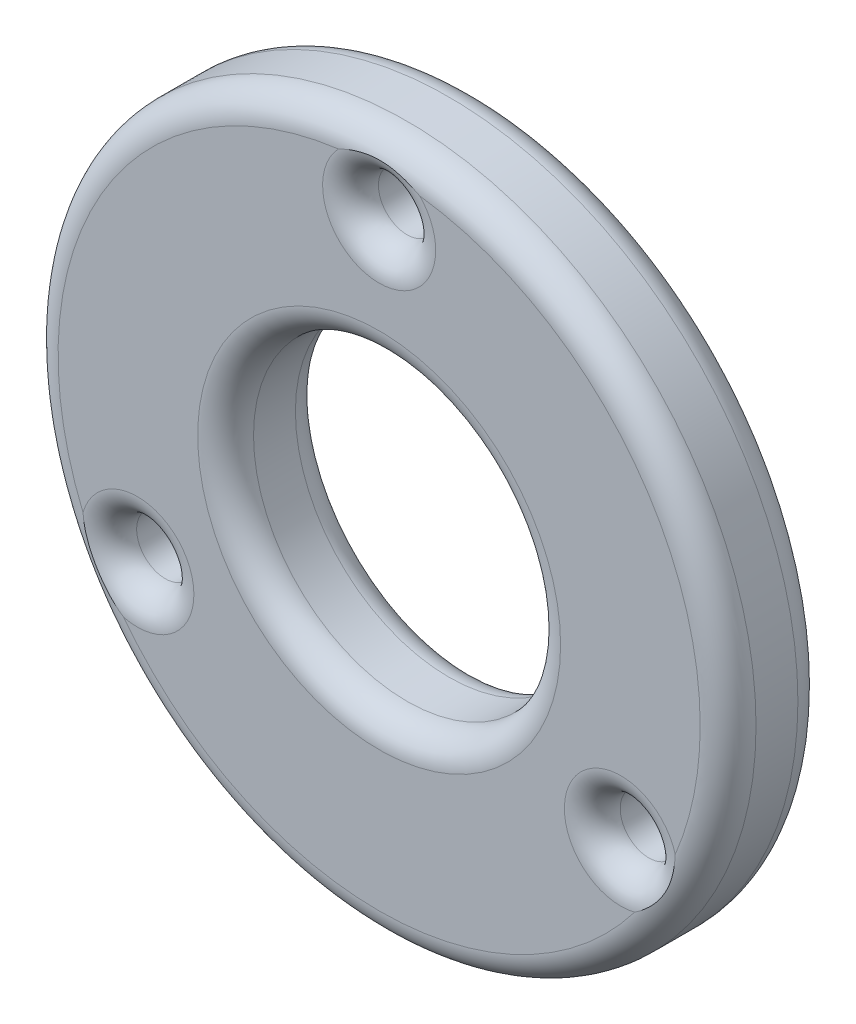
SolidWorks part; units mm, degrees
material "Nylon 101"
ref_plane "前视基准面" through (0, 0, 0) normal (0, 0, 1) x (1, 0, 0)
ref_plane "上视基准面" through (0, 0, 0) normal (0, 1, 0) x (1, 0, 0)
ref_plane "右视基准面" through (0, 0, 0) normal (1, 0, 0) x (0, 0, -1)
sketch "草图1" plane through (0, 0, 0) normal (0, 0, 1) x (1, 0, 0)
  line L0 (0, 0) -> (0, 90) construction
  circle A0 centre (0, 90) radius 11
  arc A2 (19, 72) -> (20, 75) centre (24, 72) cw
  circle A3 centre (0, 90) radius 25
  arc A5 (-19, 72) -> (-20, 75) centre (-24, 72) ccw
  circle A6 centre (0, 110) radius 2.05
  circle A7 centre (17.3205, 80) radius 2.05
  circle A8 centre (-17.3205, 80) radius 2.05
  point P30 (0, 90)
  dimension "D4" = 50
  dimension "D8" = 4.1
  dimension "D2" = 22
  dimension "D10" = 20
  dimension "D12" = 5
  dimension "D9" = 40
  dimension "D11" = 3
extrude "凸台-拉伸1" add sketch "草图1" along normal mid plane 7 contours A3 | L0 A3 A5 | L0 A2 A3 | L0 | L0 region at (-10.8641, 68.2718, 0)
fillet "圆角1" radius 2 10 edges at (25, 90, 3.5) (2.05, 110, 3.5) (19.3705, 80, 3.5) (-15.2705, 80, 3.5) (11, 90, 3.5) (25, 90, -3.5) (2.05, 110, -3.5) (19.3705, 80, -3.5) (-15.2705, 80, -3.5) (11, 90, -3.5)
